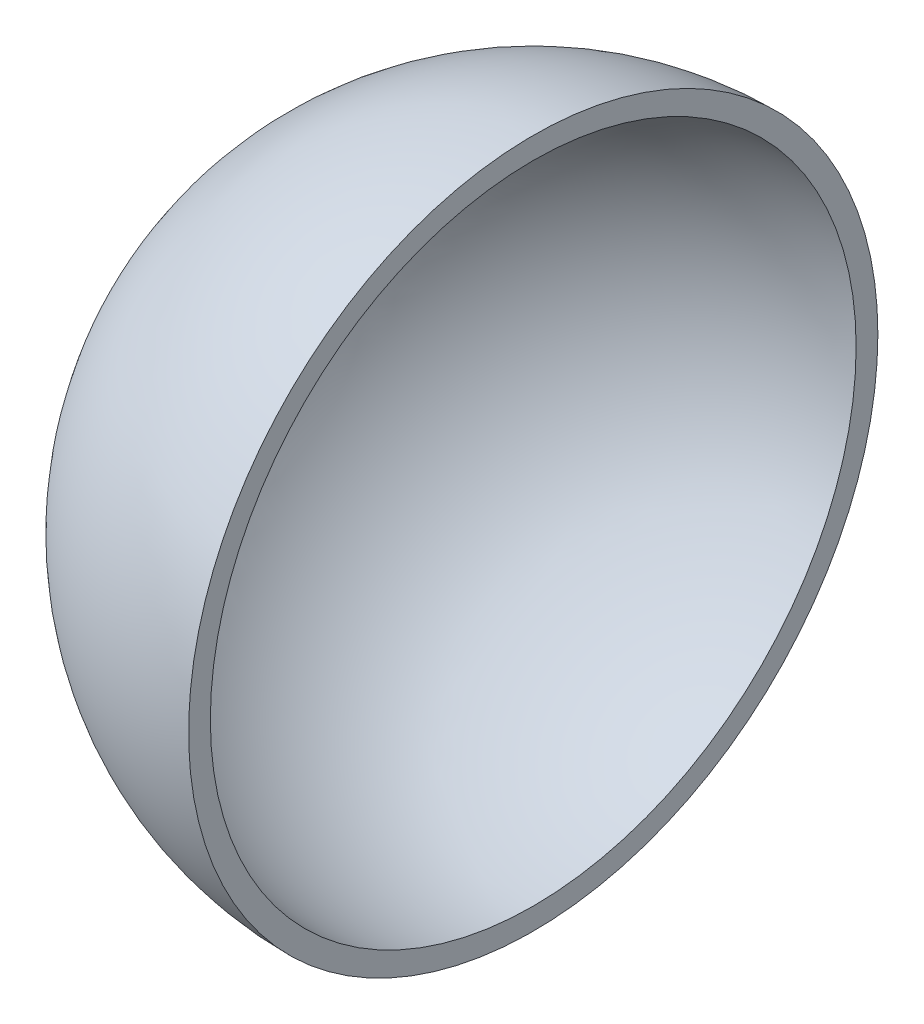
SolidWorks part; units mm, degrees
ref_plane "Front Plane" through (0, 0, 0) normal (0, 0, 1) x (1, 0, 0)
ref_plane "Top Plane" through (0, 0, 0) normal (0, 1, 0) x (1, 0, 0)
ref_plane "Right Plane" through (0, 0, 0) normal (1, 0, 0) x (0, 0, -1)
sketch "Sketch1" plane through (0, 0, 0) normal (0, 0, 1) x (1, 0, 0)
  line L0 (-184.9336, 858.1897) -> (-184.9336, 812.045)
  line L1 (-184.9336, -558.4227) -> (-184.9336, -604.5674)
  arc A0 (-184.9336, 858.1897) -> (-184.9336, -604.5674) centre (-184.9336, 126.8112) ccw
  arc A1 (-184.9336, 812.045) -> (-184.9336, -558.4227) centre (-184.9336, 126.8112) ccw
revolve "Revolve1" add sketch "Sketch1" angle 360 about L0
sketch "Sketch2" plane through (0, 0, 0) normal (0, 0, 1) x (1, 0, 0)
  line L1 (-184.9336, 858.1897) -> (601.9526, 858.1897)
  line L2 (-184.9336, 858.1897) -> (-184.9336, -705.4388)
  line L3 (-184.9336, -705.4388) -> (601.9526, -705.4388)
  line L4 (601.9526, 858.1897) -> (601.9526, -705.4388)
  circle A0 centre (-184.9336, 126.8112) radius 731.3786 construction
extrude "Cut-Extrude1" cut sketch "Sketch2" against normal blind 900 and the other way blind 1059
